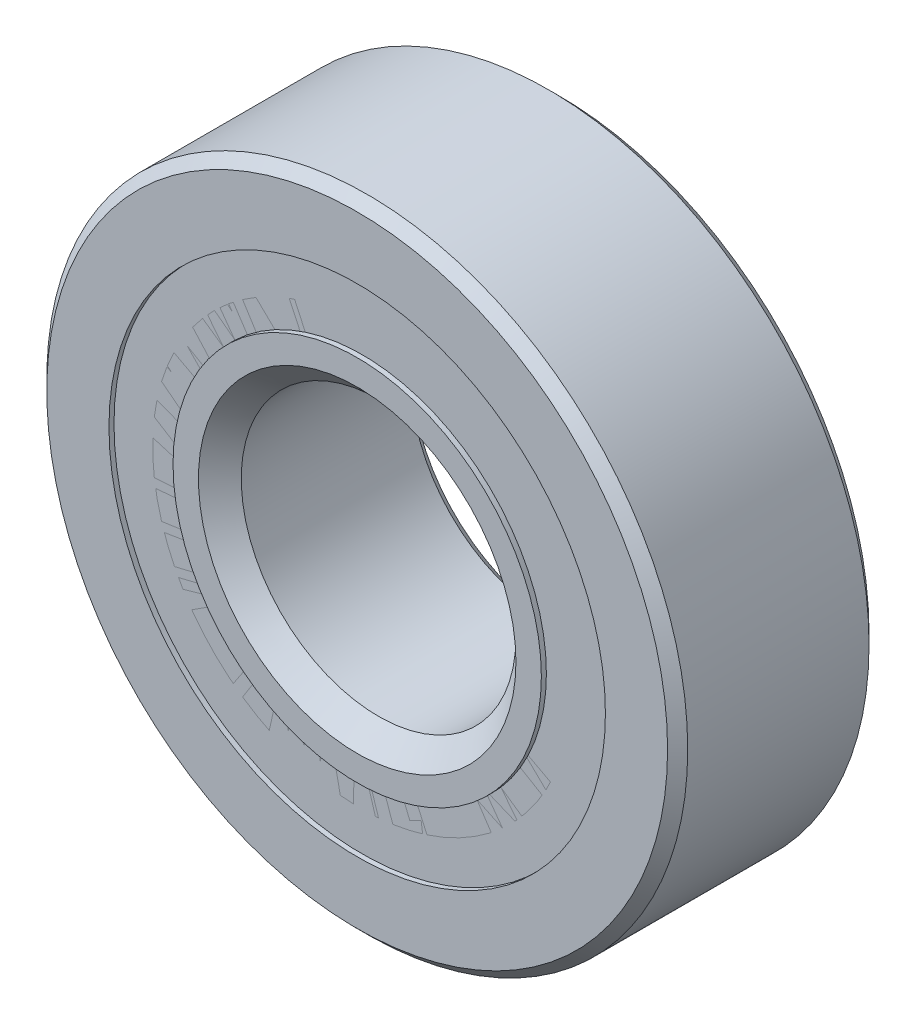
SolidWorks part; units mm, degrees
ref_plane "Front Plane" through (0, 0, 0) normal (0, 0, 1) x (1, 0, 0)
ref_plane "Top Plane" through (0, 0, 0) normal (0, 1, 0) x (1, 0, 0)
ref_plane "Right Plane" through (0, 0, 0) normal (1, 0, 0) x (0, 0, -1)
sketch "Sketch1" plane through (0, 0, 0) normal (1, 0, 0) x (0, 0, -1)
  line L0 (-5.5, 0) -> (5.5, 0) construction
  line L1 (0, 17.5) -> (0, -17.5) construction
  line L2 (4.95, 17.5) -> (-4.95, 17.5)
  line L3 (-4.95, 17.5) -> (-5.5, 16.95)
  line L4 (-5.5, 16.95) -> (-5.5, 13.5549)
  line L5 (-5.5, 13.5549) -> (-2.4444, 13.5549)
  line L6 (5.5, 13.5549) -> (2.4444, 13.5549)
  line L7 (5.5, 16.95) -> (5.5, 13.5549)
  line L8 (4.95, 17.5) -> (5.5, 16.95)
  line L9 (0, 17.5) -> (0, 12.5) construction
  line L10 (0, 12.5) -> (0, 7.5) construction
  arc A0 (-2.4444, 13.5549) -> (2.4444, 13.5549) centre (0, 12.5) cw
  point P14 (0, 7.5)
  dimension "D3" = 4.8889
  dimension "D1" = 45
  dimension "Width" = 11
  dimension "OD" = 35
  dimension "D2" = 0.55
  dimension "Shaft Dia" = 15
  dimension "D4" = 1.0549
revolve "Revolve1" add sketch "Sketch1" angle 360 about L0
sketch "Sketch2" plane through (0, 0, 0) normal (1, 0, 0) x (0, 0, -1)
  line L0 (-5.225, 11.4451) -> (-2.4444, 11.4451)
  line L1 (-5.5, 16.95) -> (-5.5, -16.95) construction
  line L2 (-5.5, 10.0569) -> (-5.225, 10.0569) construction
  line L3 (-5.225, 9.7819) -> (-4.1119, 8.6688)
  line L4 (-4.1119, 8.6688) -> (0, 8.6688)
  line L5 (0, 17.5) -> (0, -17.5) construction
  line L6 (0, 8.6688) -> (0, 9.8376)
  line L7 (0, 9.8376) -> (0, 7.5) construction
  line L8 (-5.5, 11.4451) -> (-5.5, 8.6688) construction
  line L9 (-5.5, 8.6688) -> (-4.1119, 8.6688) construction
  line L10 (-5.225, 11.4451) -> (-5.225, 9.7819)
  line L11 (-5.225, 11.4451) -> (-5.225, 17.225) construction
  line L12 (-4.95, 17.5) -> (-5.5, 16.95) construction
  arc A0 (-2.4444, 11.4451) -> (0, 9.8376) centre (0, 12.5) ccw
  arc A1 (2.4444, 13.5549) -> (-2.4444, 13.5549) centre (0, 12.5) ccw construction
  circle A2 centre (0, 12.5) radius 2.6624 construction
  dimension "D1" = 45
revolve "Revolve2" add sketch "Sketch2" angle 360 about L0
sketch "Sketch3" plane through (0, 0, 0) normal (1, 0, 0) x (0, 0, -1)
  line L0 (-5.225, 9.7819) -> (-4.1119, 8.6688)
  line L1 (-4.1119, 8.6688) -> (0, 8.6688)
  line L2 (0, 8.6688) -> (0, 9.8376)
  line L3 (-5.5, 10.0569) -> (-5.5, 8.6688)
  line L4 (-5.5, 11.4451) -> (-5.5, 8.6688) construction
  line L5 (-5.5, 8.6688) -> (-4.3312, 7.5)
  line L6 (-4.3312, 7.5) -> (4.95, 7.5)
  line L7 (4.95, 17.5) -> (4.95, -17.5) construction
  line L8 (4.95, 7.5) -> (5.5, 8.05)
  line L9 (5.5, -16.95) -> (5.5, 16.95) construction
  line L10 (5.5, 8.05) -> (5.5, 11.4451)
  line L11 (5.5, 11.4451) -> (2.4444, 11.4451)
  line L12 (-5.5, 10.0569) -> (-5.225, 10.0569)
  line L13 (4.95, 17.5) -> (5.5, 16.95) construction
  line L14 (-5.225, 10.0569) -> (-5.225, 9.7819)
  circle A0 centre (0, 12.5) radius 2.6624 construction
  arc A1 (2.4444, 11.4451) -> (0, 9.8376) centre (0, 12.5) cw
revolve "Revolve3" add sketch "Sketch3" angle 360 about L0
sketch "Sketch4" plane through (0, 0, 0) normal (1, 0, 0) x (0, 0, -1)
  line L0 (-2.6624, 12.5) -> (2.6624, 12.5)
  circle A1 centre (0, 12.5) radius 2.6624 construction
  arc A2 (-2.6624, 12.5) -> (2.6624, 12.5) centre (0, 12.5) cw
  arc A3 (2.4444, 13.5549) -> (-2.4444, 13.5549) centre (0, 12.5) ccw construction
revolve "Revolve4" add sketch "Sketch4" angle 360 about L0
ref_axis "Axis1" through (0, 0, -5.5) along (0, 0, 1)
pattern_circular "CirPattern1" count 8 every 45 about axis through (0, 0, -5.5) along (0, 0, 1) of bodies 104
sketch "Sketch5" plane through (0, 0, 0) normal (1, 0, 0) x (0, 0, -1)
  line L0 (-5.5, 13.5549) -> (-2.4444, 13.5549) construction
  line L1 (-5.225, 13.5549) -> (-2.6624, 13.5549)
  line L2 (-5.225, 13.5549) -> (-5.225, 10.0569)
  line L3 (-5.225, 10.0569) -> (-2.6624, 10.0569)
  line L4 (-2.6624, 13.5549) -> (-2.6624, 10.0569)
  line L6 (-4.95, 17.5) -> (-5.5, 16.95) construction
  line L7 (0, 17.5) -> (0, 7.5) construction
  line L8 (5.225, 10.0569) -> (2.6624, 10.0569)
  line L9 (2.6624, 13.5549) -> (2.6624, 10.0569)
  line L10 (5.225, 13.5549) -> (2.6624, 13.5549)
  line L11 (5.225, 13.5549) -> (5.225, 10.0569)
  circle A0 centre (0, 12.5) radius 2.6624 construction
  point P10 (-5.225, 17.225)
revolve "Revolve5" add sketch "Sketch5" angle 360 about L0
equation "\"D2@Sketch1\" = \"Width@Sketch1\"*.05"
equation "\"D3@Sketch1\" = \"Width@Sketch1\"/2.25"
equation "\"D4@Sketch1\" = (((\"OD@Sketch1\"-\"Width@Sketch1\")/2)/3.25)/3.5"
equation "\"D2@CirPattern1\" = 360/\"Balls@CirPattern1\""
